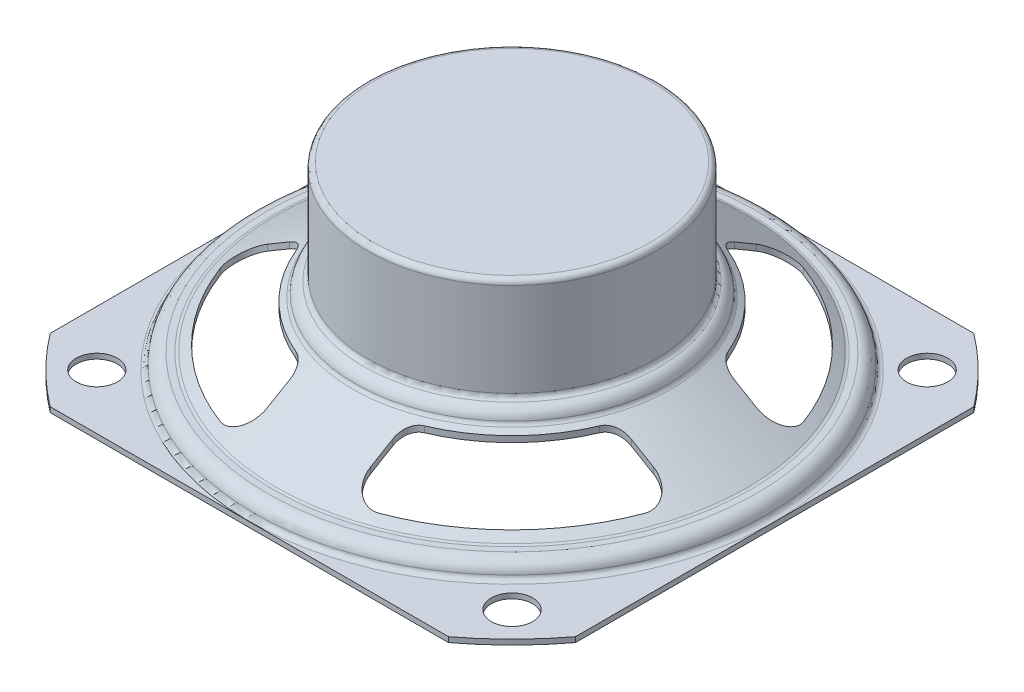
SolidWorks part; units mm, degrees
ref_plane "Front Plane" through (0, 0, 0) normal (0, 0, 1) x (1, 0, 0)
ref_plane "Top Plane" through (0, 0, 0) normal (0, 1, 0) x (1, 0, 0)
ref_plane "Right Plane" through (0, 0, 0) normal (1, 0, 0) x (0, 0, -1)
sketch "Sketch1" plane through (0, 0, 0) normal (0, 0, 1) x (1, 0, 0)
  line L0 (0, -2495.5464) -> (0, 122281.7753) construction
  line L1 (0, 0) -> (32, 0)
  line L2 (32, 0) -> (32, 0.5)
  line L3 (32, 0.5) -> (25, 0.5)
  line L4 (25, 0.5) -> (25, 2)
  line L5 (25, 2) -> (23, 2)
  line L6 (23, 2) -> (15.25, 6.75)
  line L7 (15.25, 6.75) -> (15.25, 8)
  line L8 (15.25, 8) -> (14, 8)
  line L9 (14, 8) -> (14, 18)
  line L10 (14, 18) -> (0, 18)
  line L11 (0, 18) -> (0, 0)
  dimension "D1" = 32
  dimension "D2" = 25
  dimension "D3" = 23
  dimension "D4" = 10
  dimension "D5" = 1.25
  dimension "D6" = 1.25
  dimension "D7" = 14
  dimension "D8" = 18
  dimension "D9" = 0.5
  dimension "D10" = 1.5
revolve "Revolve1" add sketch "Sketch1" angle 360 about L0
shell "Shell1" thickness 0.5
fillet "Fillet1" radius 1.25 2 edges at (25, 2, 0) (15.25, 8, 0)
sketch "Sketch2" plane through (0, 0.5, 0) normal (0, 1, 0) x (1, 0, 0)
  line L0 (-25.5, 20) -> (-20, 25.5)
  line L5 (-20, -25.5) -> (20, -25.5)
  line L6 (-25.5, -20) -> (-25.5, 20)
  line L7 (-20, 25.5) -> (20, 25.5)
  line L8 (25.5, -20) -> (25.5, 20)
  line L9 (-25.5, -25.5) -> (25.5, 25.5) construction
  line L10 (-25.5, 25.5) -> (25.5, -25.5) construction
  line L11 (-25.5, -20) -> (-20, -25.5)
  line L12 (20, -25.5) -> (25.5, -20)
  line L13 (20, 25.5) -> (25.5, 20)
  circle A0 centre (0, 0) radius 35.0821
  point P0 (0, 0)
  dimension "D1" = 51
  dimension "D2" = 51
extrude "Cut-Extrude1" cut sketch "Sketch2" against normal up to next
fillet "Fillet2" radius 0.5 8 edges at (25, 0.5, 0) (23, 2, 0) (14.75, 6.47, 0) (-13.5, 7.5, 0) (-13.5, 17.5, 0) (14, 18, 0) (15.25, 6.75, 0) (14, 8, 0)
sketch "Sketch3" plane through (0, 0.5, 0) normal (0, 1, 0) x (1, 0, 0)
  line L0 (-22.6274, 22.6274) -> (22.6274, -22.6274) construction
  line L1 (31.564, 0) -> (0, 0) construction
  line L2 (0, 0) -> (0, -29.3396) construction
  line L3 (0, -29.3396) -> (5, -29.3396) construction
  line L4 (5, -29.3396) -> (5, -5) construction
  line L5 (5, -5) -> (31.564, -5) construction
  line L6 (5, -16.5831) -> (5, -18.735)
  line L7 (16.5831, -5) -> (18.735, -5)
  arc A0 (-19.3326, 25.5) -> (-25.5, 19.3326) centre (0, 0) ccw construction
  arc A1 (19.3326, -25.5) -> (25.5, -19.3326) centre (0, 0) ccw construction
  circle A2 centre (20.1525, -20.1525) radius 2
  arc A3 (14.7406, -6.2222) -> (6.2222, -14.7406) centre (0, 0) cw
  arc A4 (20.6085, -7.7) -> (7.7, -20.6085) centre (0, 0) cw
  arc A5 (20.6085, -7.7) -> (18.735, -5) centre (18.735, -7) ccw
  arc A6 (14.7406, -6.2222) -> (16.5831, -5) centre (16.5831, -7) cw
  arc A7 (7.7, -20.6085) -> (5, -18.735) centre (7, -18.735) cw
  arc A8 (6.2222, -14.7406) -> (5, -16.5831) centre (7, -16.5831) ccw
  point P23 (21.4243, -5)
  point P26 (15.1987, -5)
  point P29 (5, -21.4243)
  point P32 (5, -15.1987)
  dimension "D1" = 4
  dimension "D4" = 16
  dimension "D5" = 22
  dimension "D6" = 2
  dimension "D2" = 3.5
  dimension "D3" = 5
extrude "Cut-Extrude2" cut sketch "Sketch3" against normal mid plane 14
pattern_circular "CirPattern1" count 4 over 360 about axis through (0, 0, 0) along (0, 1, 0) of "Cut-Extrude2"
